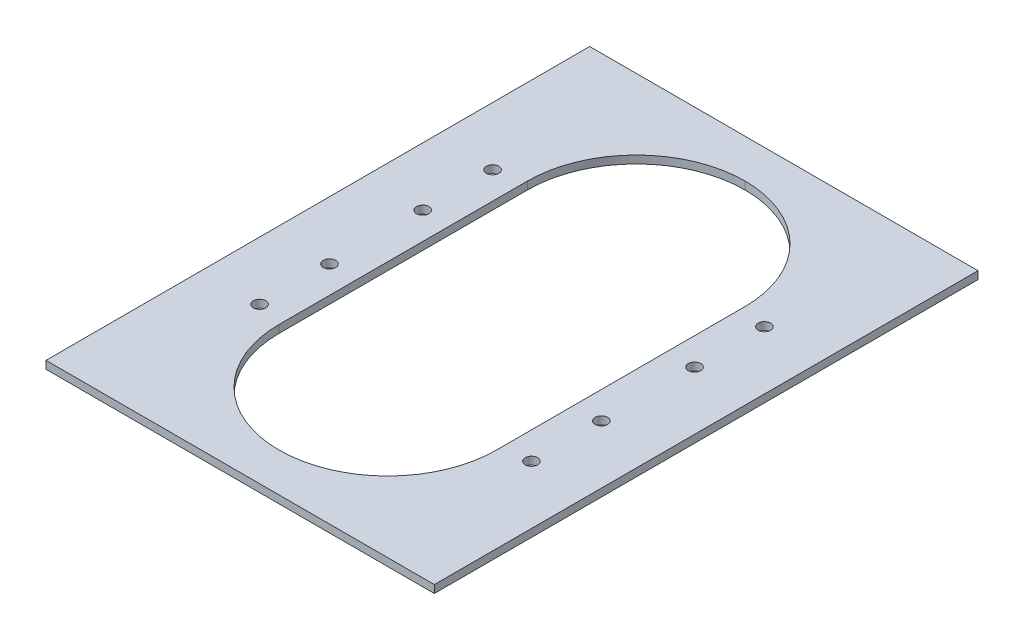
SolidWorks part; units mm, degrees
ref_plane "前基準面" through (0, 0, 0) normal (0, 0, 1) x (1, 0, 0)
ref_plane "上基準面" through (0, 0, 0) normal (0, 1, 0) x (1, 0, 0)
ref_plane "右基準面" through (0, 0, 0) normal (1, 0, 0) x (0, 0, -1)
sketch "草圖1" plane through (0, 0, 0) normal (0, 1, 0) x (1, 0, 0)
  line L0 (0, -16.8818) -> (0, 16.8818) construction
  line L1 (-50, -70) -> (50, -70)
  line L2 (-50, -70) -> (-50, 70)
  line L3 (-50, 70) -> (50, 70)
  line L4 (50, -70) -> (50, 70)
  line L5 (-50, 0) -> (50, 70) construction
  line L6 (-50, 70) -> (50, 0) construction
  line L7 (-28, -60) -> (28, -60)
  line L8 (-28, 60) -> (28, 60)
  line L9 (-28, 60) -> (-28, -60)
  line L10 (-88.3678, 0) -> (88.3678, 0) construction
  line L11 (28, 60) -> (28, -60)
  line L12 (0, -27.4719) -> (0, 60) construction
  line L13 (-28, 0) -> (28, 0) construction
  circle A0 centre (-35, 30) radius 1.6
  circle A1 centre (35, 30) radius 1.6
  circle A2 centre (-35, 12) radius 1.6
  circle A3 centre (35, 12) radius 1.6
  circle A4 centre (35, -12) radius 1.6
  circle A5 centre (35, -30) radius 1.6
  circle A6 centre (-35, -30) radius 1.6
  circle A7 centre (-35, -12) radius 1.6
  point P0 (0, 35)
  point P7 (0, 0)
  point P9 (0, 35)
  point P10 (28, -56.7206)
  point P12 (28, 0)
  point P31 (0, 0)
  point P32 (0, 0)
  point P33 (28, 0)
  point P34 (50, 4)
  point P35 (50, 84)
  point P36 (50, 4)
  point P37 (0, 92.2078)
  point P38 (0, 0)
  point P43 (-28, 0)
  point P44 (28, -50.3332)
  dimension "D5" = 3.2
  dimension "D1" = 56
  dimension "D2" = 100
  dimension "D3" = 140
  dimension "D4" = 70
  dimension "D6" = 10
  dimension "D8" = 18
  dimension "D9" = 24
extrude "填料-伸長1" add sketch "草圖1" along normal blind 2
fillet "圓角1" radius 28 4 edges at (28, 1, -60) (-28, 1, -60) (-28, 1, 60) (28, 1, 60)
